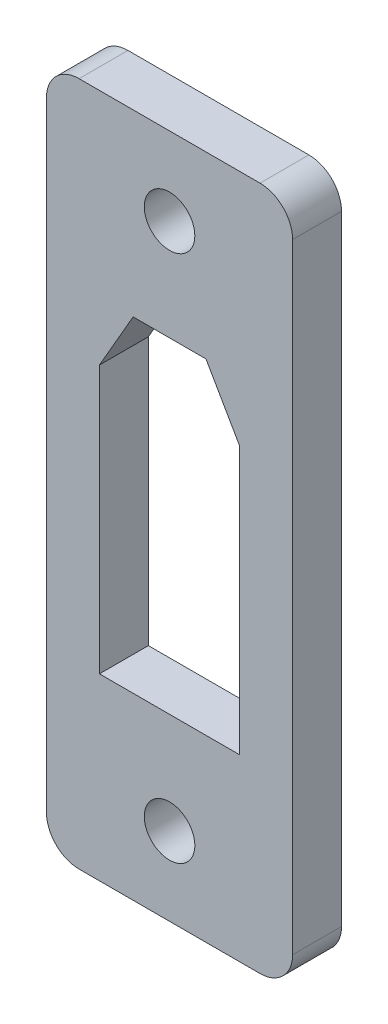
SolidWorks part; units mm, degrees
ref_plane "Front Plane" through (0, 0, 0) normal (0, 0, 1) x (1, 0, 0)
ref_plane "Top Plane" through (0, 0, 0) normal (0, 1, 0) x (1, 0, 0)
ref_plane "Right Plane" through (0, 0, 0) normal (1, 0, 0) x (0, 0, -1)
sketch "Sketch1" plane through (0, 0, 0) normal (0, 0, 1) x (1, 0, 0)
  line L0 (-9.7546, 0) -> (15.1169, 0) construction
  line L1 (-7.55, 21) -> (7.55, 21)
  line L2 (-7.55, 21) -> (-7.55, -21)
  line L3 (-7.55, -21) -> (7.55, -21)
  line L4 (7.55, 21) -> (7.55, -21)
  line L5 (-7.55, 21) -> (7.55, -21) construction
  line L6 (-7.55, -21) -> (7.55, 21) construction
  circle A0 centre (0, 16.2) radius 1.55
  circle A1 centre (0, -16.2) radius 1.55
  point P0 (0, 0)
  point P12 (0, 0)
  dimension "D3" = 3.1
  dimension "D1" = 42
  dimension "D2" = 15.1
  dimension "D4" = 32.4
extrude "Boss-Extrude1" add sketch "Sketch1" along normal blind 3
fillet "Fillet1" radius 2 4 edges at (-7.55, -21, 1.5) (7.55, -21, 1.5) (-7.55, 21, 1.5) (7.55, 21, 1.5)
sketch "Sketch2" plane through (0, 0, 3) normal (0, 0, 1) x (1, 0, 0)
  line L0 (-4.3, 6.4108) -> (-4.3, -10)
  line L1 (-4.3, -10) -> (4.3, -10)
  line L2 (-4.3, 6.4108) -> (-2.2347, 10)
  line L3 (-2.2347, 10) -> (2.2347, 10)
  line L4 (0, 10) -> (0, -10) construction
  line L5 (4.3, 6.4108) -> (2.2347, 10)
  line L6 (4.3, 6.4108) -> (4.3, -10)
  point P2 (0, 0)
  point P10 (-4.3, 6.4108)
  point P11 (-2.2347, 10)
  dimension "D1" = 20
  dimension "D2" = 8.6
extrude "Cut-Extrude1" cut sketch "Sketch2" against normal through all
